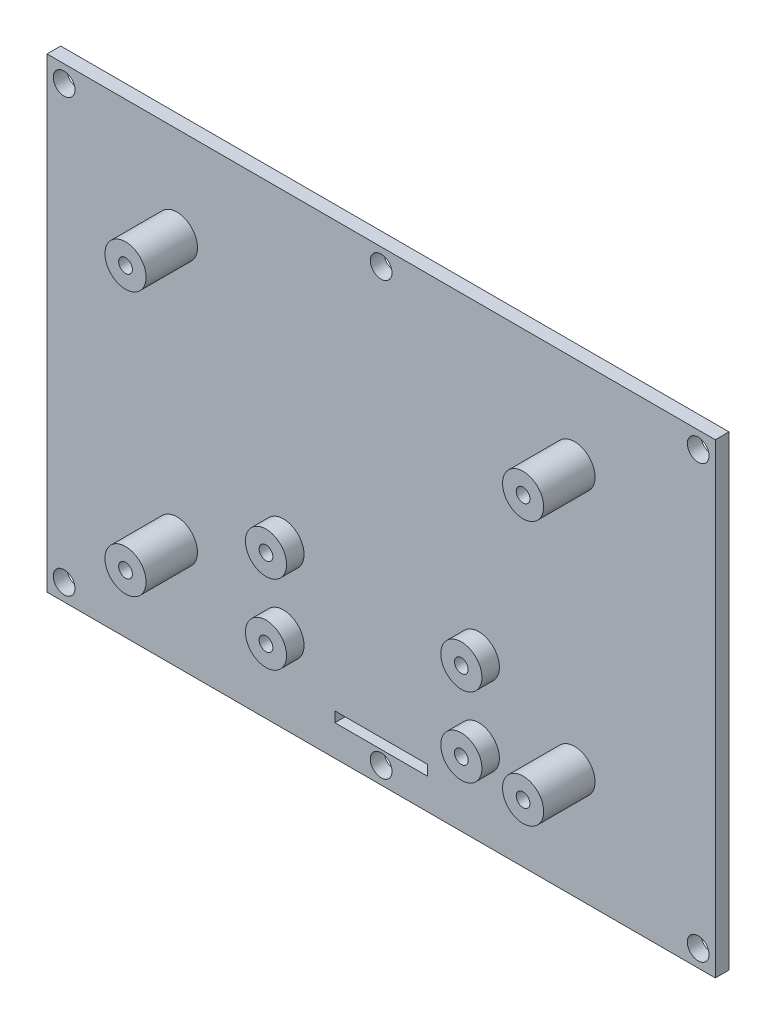
SolidWorks part; units mm, degrees
ref_plane "Front Plane" through (0, 0, 0) normal (0, 0, 1) x (1, 0, 0)
ref_plane "Top Plane" through (0, 0, 0) normal (0, 1, 0) x (1, 0, 0)
ref_plane "Right Plane" through (0, 0, 0) normal (1, 0, 0) x (0, 0, -1)
sketch "Sketch1" plane through (0, 0, 0) normal (0, 0, 1) x (1, 0, 0)
  line L1 (85.5, -56) -> (-85.5, -56)
  line L2 (85.5, -56) -> (85.5, 56)
  line L3 (85.5, 56) -> (-85.5, 56)
  line L4 (-85.5, -56) -> (-85.5, 56)
  line L5 (85.5, -56) -> (-85.5, 56) construction
  line L6 (85.5, 56) -> (-85.5, -56) construction
  line L11 (80, -45) -> (-80, -45)
  line L12 (80, -45) -> (80, 51)
  line L13 (80, 51) -> (-80, 51)
  line L14 (-80, -45) -> (-80, 51)
  line L15 (80, -45) -> (-80, 51) construction
  line L16 (80, 51) -> (-80, -45) construction
  line L17 (-13.5, -56) -> (13.5, -56)
  line L18 (-13.5, -56) -> (-13.5, -59)
  line L19 (-13.5, -59) -> (13.5, -59)
  line L20 (13.5, -56) -> (13.5, -59)
  line L21 (97.5, 68) -> (-97.5, 68)
  line L22 (97.5, 68) -> (97.5, -68)
  line L23 (97.5, -68) -> (-97.5, -68)
  line L24 (-97.5, 68) -> (-97.5, -68)
  line L25 (97.5, 68) -> (-97.5, -68) construction
  line L26 (97.5, -68) -> (-97.5, 68) construction
  point P0 (0, 0)
  point P6 (0, 0)
  point P7 (0, 3)
  point P16 (0, 0)
  dimension "D1" = 171
  dimension "D2" = 112
  dimension "D3" = 96
  dimension "D4" = 160
  dimension "D5" = 5
  dimension "D6" = 72
  dimension "D7" = 27
  dimension "D8" = 3
  dimension "D9" = 12
  dimension "D10" = 17.5
  dimension "D11" = 12
extrude "Boss-Extrude1" add sketch "Sketch1" against normal blind 2 contours L4 L1 L2 L3 L11 L14 L13 L12 | L21 L24 L23 L22 L1 L20 L19 L18 L4 L3 L2 | L14 L11 L12 L13 region at (49.5, -53.9559, 0) region at (0, 3, 0) region at (95.1226, 0, 0)
extrude "Boss-Extrude2" add sketch "Sketch1<3>" along normal blind 2 contours L21 L24 L23 L22 L1 L20 L19 L18 L4 L3 L2 | L4 L1 L2 L3 L11 L14 L13 L12 | L14 L11 L12 L13 region at (49.5, -53.9559, 0) region at (0, 3, 0) region at (95.1226, 0, 0)
sketch "Sketch1<3>" plane through (0, 0, 0) normal (0, 0, 1) x (1, 0, 0) same geometry as "Sketch1"
sketch "Sketch2" plane through (0, 0, 2) normal (0, 0, 1) x (1, 0, 0)
  line L0 (97.5, 68) -> (-97.5, 68) construction
  line L1 (92.5, -63) -> (-92.5, -63) construction
  line L2 (92.5, -63) -> (92.5, 63) construction
  line L3 (92.5, 63) -> (-92.5, 63) construction
  line L4 (-92.5, -63) -> (-92.5, 63) construction
  line L5 (92.5, -63) -> (-92.5, 63) construction
  line L6 (92.5, 63) -> (-92.5, -63) construction
  line L7 (-97.5, 68) -> (-97.5, -68) construction
  circle A0 centre (-92.5, 63) radius 3.175
  circle A1 centre (0, 63) radius 3.175
  circle A2 centre (92.5, 63) radius 3.175
  circle A3 centre (92.5, -63) radius 3.175
  circle A4 centre (0, -63) radius 3.175
  circle A5 centre (-92.5, -63) radius 3.175
  point P0 (0, 0)
  dimension "D1" = 6.35
  dimension "D2" = 5
  dimension "D3" = 5
extrude "Cut-Extrude1" cut sketch "Sketch2" against normal through all
sketch "Sketch3" plane through (0, 0, 2) normal (0, 0, 1) x (1, 0, 0)
  line L0 (-13.5, -59) -> (13.5, -59) construction
  line L1 (28.5, -44) -> (-28.5, -44) construction
  line L2 (28.5, -44) -> (28.5, -21) construction
  line L3 (28.5, -21) -> (-28.5, -21) construction
  line L4 (-28.5, -44) -> (-28.5, -21) construction
  line L5 (28.5, -44) -> (-28.5, -21) construction
  line L6 (28.5, -21) -> (-28.5, -44) construction
  line L11 (-12.1109, -44) -> (11.8889, -44) construction
  line L13 (-12.1109, -44) -> (-12.1109, -40) construction
  line L14 (-12.1109, -40) -> (11.8889, -40) construction
  line L15 (11.8889, -44) -> (11.8889, -40) construction
  line L16 (13.5, -56) -> (-13.5, -56) construction
  circle A0 centre (-28.5, -44) radius 6
  circle A1 centre (-28.5, -44) radius 2
  point P17 (-28.5, -21)
  point P18 (28.5, -21)
  point P19 (28.5, -44)
  point P21 (0, -56)
  point P22 (0, -44)
  dimension "D1" = 4
  dimension "D2" = 12
  dimension "D3" = 57
  dimension "D4" = 23
  dimension "D5" = 4
  dimension "D6" = 19
extrude "Boss-Extrude3" add sketch "Sketch3" along normal blind 5.1
pattern_sketch "Sketch-Pattern1" of "Boss-Extrude3" driven by "Sketch3"
sketch "Sketch4" plane through (0, 0, 2) normal (0, 0, 1) x (1, 0, 0)
  line L0 (-59.586, 40.9925) -> (56.414, 40.9925) construction
  line L1 (-59.586, 40.9925) -> (-59.586, -36.0075) construction
  line L2 (-59.586, -36.0075) -> (56.414, -36.0075) construction
  line L3 (56.414, 40.9925) -> (56.414, -36.0075) construction
  line L4 (-59.586, 40.9925) -> (56.414, -36.0075) construction
  line L5 (-59.586, -36.0075) -> (56.414, 40.9925) construction
  circle A0 centre (-59.586, -36.0075) radius 6
  circle A1 centre (-59.586, -36.0075) radius 2
  circle A2 centre (-28.5, -21) radius 6 construction
  circle A3 centre (-28.5, -21) radius 2 construction
  point P4 (-59.586, 40.9925)
  point P5 (56.414, 40.9925)
  point P6 (56.414, -36.0075)
  point P7 (-59.586, -36.0075)
  dimension "D1" = 116
  dimension "D2" = 77
extrude "Boss-Extrude6" add sketch "Sketch4" along normal blind 15 contours A0 A1 region at (-65.4163, -36.0075, 2)
pattern_sketch "Sketch-Pattern2" of "Boss-Extrude6" driven by "Sketch4"
